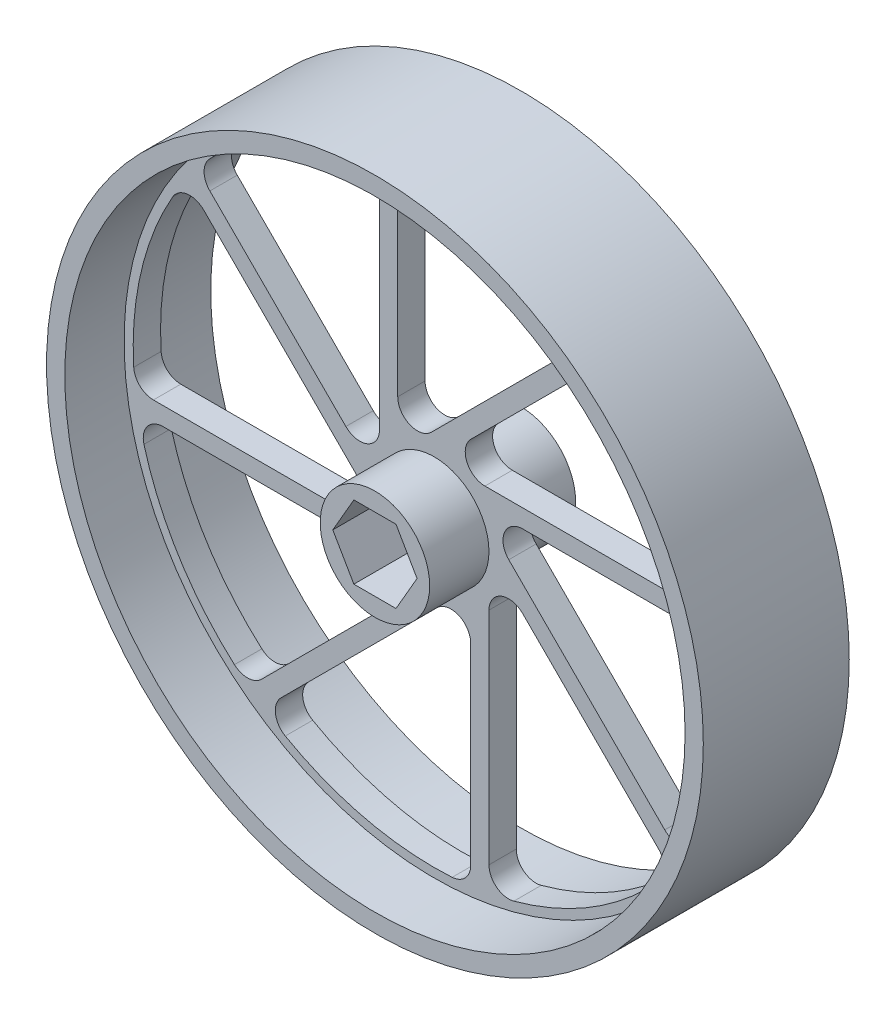
SolidWorks part; units mm, degrees
material "6061-T6 (SS)"
ref_plane "Front Plane" through (0, 0, 0) normal (0, 0, 1) x (1, 0, 0)
ref_plane "Top Plane" through (0, 0, 0) normal (0, 1, 0) x (1, 0, 0)
ref_plane "Right Plane" through (0, 0, 0) normal (1, 0, 0) x (0, 0, -1)
sketch "Sketch1" plane through (0, 0, 0) normal (0, 0, 1) x (1, 0, 0)
  line L1 (3.6662, -6.35) -> (7.3323, 0)
  line L2 (7.3323, 0) -> (3.6662, 6.35)
  line L3 (3.6662, 6.35) -> (-3.6662, 6.35)
  line L4 (-3.6662, 6.35) -> (-7.3323, 0)
  line L5 (-7.3323, 0) -> (-3.6662, -6.35)
  line L6 (-3.6662, -6.35) -> (3.6662, -6.35)
  circle A0 centre (0, 0) radius 57.15
  circle A1 centre (0, 0) radius 6.35 construction
  dimension "D1" = 114.3
  dimension "D2" = 12.7
extrude "Boss-Extrude1" add sketch "Sketch1" along normal mid plane 25.4
sketch "Sketch2" plane through (0, 0, 12.7) normal (0, 0, 1) x (1, 0, 0)
  circle A0 centre (0, 0) radius 9.525
  circle A1 centre (0, 0) radius 53.975
  circle A2 centre (0, 0) radius 57.15 construction
  dimension "D1" = 3.175
  dimension "D2" = 19.05
extrude "Cut-Extrude1" cut sketch "Sketch2" against normal through all
sketch "Sketch4" plane through (0, 0, 0) normal (0, 0, 1) x (1, 0, 0)
  line L0 (-9.525, 0) -> (-9.525, 53.1279)
  line L1 (-6.35, 7.0995) -> (-6.35, 53.6002)
  circle A2 centre (0, 0) radius 9.525 construction
  circle A3 centre (0, 0) radius 53.975 construction
  arc A4 (-6.35, 53.6002) -> (-9.525, 53.1279) centre (0, 0) ccw
  arc A5 (-6.35, 7.0995) -> (-9.525, 0) centre (0, 0) ccw
  point P8 (40.2587, 35.0654)
  point P9 (-6.3497, 53.1283)
  dimension "D1" = 3.175
extrude "Boss-Extrude2" add sketch "Sketch4" along normal mid plane 4.7625
sketch "Sketch5" plane through (0, 0, 2.3813) normal (0, 0, 1) x (1, 0, 0)
  circle A0 centre (0, 0) radius 53.975
  circle A1 centre (0, 0) radius 52.3875
  circle A2 centre (0, 0) radius 53.975 construction
  circle A3 centre (0, 0) radius 57.15 construction
  dimension "D1" = 4.7625
extrude "Boss-Extrude3" add sketch "Sketch5" against normal up to surface (4.7625 mm away) up to face at (-8.1278, 28.5475, -2.3812)
fillet "Fillet1" radius 3.429 2 edges at (-9.525, 51.5143, 0) (-6.35, 52.0012, 0)
pattern_circular "CirPattern1" count 8 over 360 about axis through (0, 0, 12.7) along (0, 0, -1) of "Boss-Extrude2", "Fillet1"
fillet "Fillet2" radius 3.429 8 edges at (0.5447, 9.525, 0) (-6.35, 7.1204, 0) (-9.525, 0.5447, 0) (-7.1204, -6.35, 0) (-0.5447, -9.525, 0) (6.35, -7.1204, 0) (9.525, -0.5447, 0) (7.1204, 6.35, 0)
